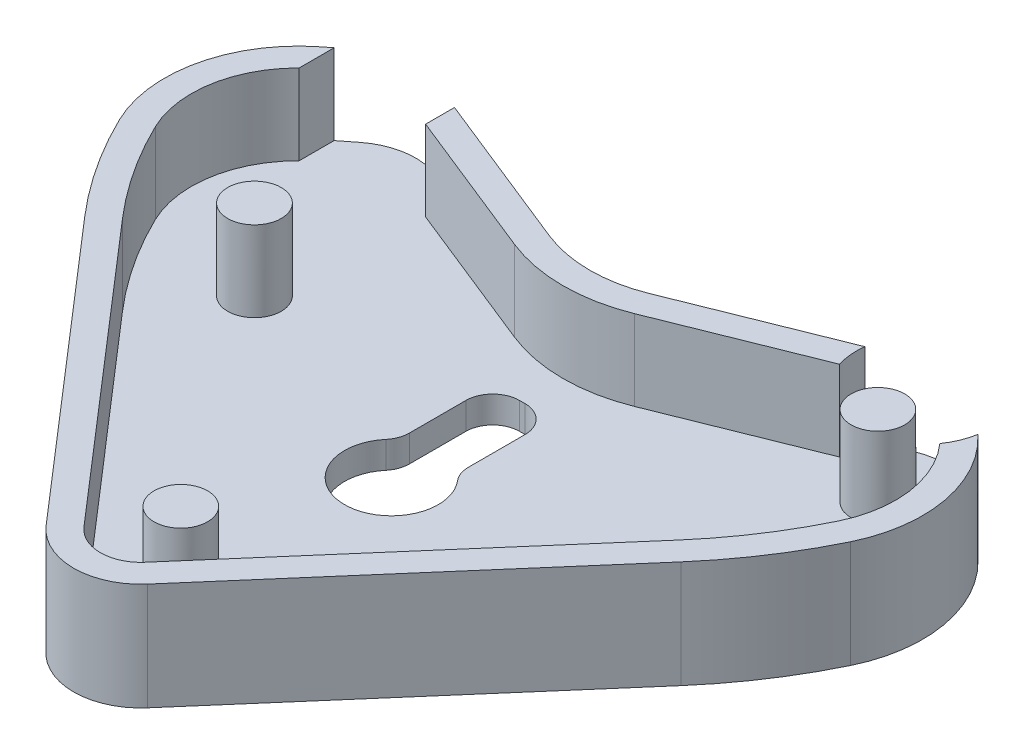
SolidWorks part; units mm, degrees
ref_plane "Alzado" through (0, 0, 0) normal (0, 0, 1) x (1, 0, 0)
ref_plane "Planta" through (0, 0, 0) normal (0, 1, 0) x (1, 0, 0)
ref_plane "Vista lateral" through (0, 0, 0) normal (1, 0, 0) x (0, 0, -1)
sketch "Croquis1" plane through (0, 0, 0) normal (0, 1, 0) x (1, 0, 0)
  line L0 (0, 0) -> (0, -34.6622) construction
  line L1 (0, 0) -> (-30, 0) construction
  line L2 (0, 0) -> (30, 0) construction
  line L3 (0, 0) -> (0, 11.4382) construction
  line L4 (-30, 0) -> (-30, 6.56)
  line L5 (-30, 6.56) -> (-20.5613, 13.9702)
  line L6 (-20.5613, 13.9702) -> (0, 5.7191)
  line L7 (0, 5.7191) -> (20.5613, 13.9702)
  line L8 (20.5613, 13.9702) -> (30, 6.56)
  line L9 (30, 6.56) -> (30, 0)
  line L10 (-30, 0) -> (0, -34.6622)
  line L11 (0, -34.6622) -> (30, 0)
  dimension "D1" = 30
  dimension "D2" = 30
  dimension "D3" = 12
  dimension "D4" = 12
  dimension "D5" = 120
  dimension "D6" = 120
extrude "Saliente-Extruir1" add sketch "Croquis1" along normal blind 8
fillet "Redondeo3" radius 5 1 edges at (0, 4, 34.6622)
fillet "Redondeo4" radius 5 2 edges at (20.5613, 4, -13.9702) (-20.5613, 4, -13.9702)
fillet "Redondeo5" radius 35 2 edges at (-30, 4, 0) (30, 4, 0)
fillet "Redondeo6" radius 10 2 edges at (-30, 4, -6.56) (30, 4, -6.56)
fillet "Redondeo7" radius 10 1 edges at (0, 4, -5.7191)
shell "Vaciado1" thickness 2 removed face at (0, 8, -0.3452)
sketch "Croquis2" plane through (0, 2, 0) normal (0, 1, 0) x (1, 0, 0)
  line L0 (0, 4.4942) -> (0, -30.0219) construction
  arc A0 (-4.4691, 5.3575) -> (4.4691, 5.3575) centre (0, 16.4942) ccw construction
  arc A1 (-2.2684, -28.9851) -> (2.2684, -28.9851) centre (0, -27.0219) ccw construction
  circle A2 centre (0, -24.0219) radius 2
  dimension "D2" = 4
  dimension "D1" = 6
extrude "Saliente-Extruir2" add sketch "Croquis2" along normal through all
sketch "Croquis3" plane through (0, 2, 0) normal (0, 1, 0) x (1, 0, 0)
  circle A0 centre (20.1688, 11.2246) radius 5
  arc A1 (21.5969, 10.6144) -> (18.627, 11.0389) centre (19.7443, 8.2548) ccw construction
  dimension "D1" = 10
extrude "Cortar-Extruir1" cut sketch "Croquis3" along normal blind 10
sketch "Croquis4" plane through (0, 2, 0) normal (0, 1, 0) x (1, 0, 0)
  line L0 (20.4518, 13.2044) -> (19.7443, 8.2548) construction
  line L1 (19.7443, 8.2548) -> (-19.2557, 8.2548) construction
  arc A0 (22.8319, 12.1876) -> (17.8822, 12.8951) centre (19.7443, 8.2548) ccw construction
  circle A1 centre (19.7443, 8.2548) radius 2
  dimension "D1" = 4
  dimension "D2" = 39
extrude "Saliente-Extruir4" add sketch "Croquis4" along normal through all
sketch "Croquis5" plane through (0, 2, 0) normal (0, 1, 0) x (1, 0, 0)
  line L0 (0, -24.0219) -> (0, 9.8307) construction
  line L1 (19.7443, 8.2548) -> (0, 8.2548) construction
  line L2 (0, 8.2548) -> (-19.74, 8.2548) construction
  line L3 (-23.9156, 8.2548) -> (-15.5644, 8.2548)
  line L4 (-15.5644, 8.2548) -> (-15.5644, 14.1742)
  line L5 (-15.5644, 14.1742) -> (-23.9156, 14.1742)
  line L6 (-23.9156, 14.1742) -> (-23.9156, 7.8399)
  point P11 (-19.74, 8.2548)
  line M7 (-4.4691, 5.3575) -> (-18.627, 11.0389)
  arc M8 (-18.627, 11.0389) -> (-21.5969, 10.6144) centre (-19.7443, 8.2548) ccw
  line M9 (-21.5969, 10.6144) -> (-23.2237, 9.3372)
  arc M10 (-23.2237, 9.3372) -> (-25.4814, -0.4469) centre (-18.2836, 3.0448) ccw
  dimension "D1" = 19.74
extrude "Cortar-Extruir2" cut sketch "Croquis5" along normal blind 10 contours L5 L6 L4 M10 M9 M8 M7 region at (-19.8852, 2, -12.259)
sketch "Croquis6" plane through (0, 2, 0) normal (0, 1, 0) x (1, 0, 0)
  line L0 (-16.8551, -1.6721) -> (-24.8551, -1.6721) construction
  line L1 (-16.8551, -1.6721) -> (-16.8551, 10.3279) construction
  line L2 (-4.4691, 5.3575) -> (-15.5644, 9.8099) construction
  circle A0 centre (-16.8551, -1.6721) radius 2
  arc A2 (-25.4814, -0.4469) -> (-20.7426, -7.64) centre (4.2096, 13.9561) ccw construction
  dimension "D1" = 4
  dimension "D2" = 8
  dimension "D3" = 12
extrude "Saliente-Extruir5" add sketch "Croquis6" along normal through all
sketch "Croquis7" plane through (0, 2, 0) normal (0, 1, 0) x (1, 0, 0)
  line L2 (0, 4.4942) -> (0, -30.0219) construction
  arc A0 (-4.4691, 5.3575) -> (4.4691, 5.3575) centre (0, 16.4942) ccw construction
  circle A1 centre (0, -8.3059) radius 2.5
  arc A2 (-2.2684, -28.9851) -> (2.2684, -28.9851) centre (0, -27.0219) ccw construction
  dimension "D1" = 5
  dimension "D2" = 0
extrude "Cortar-Extruir3" cut sketch "Croquis7" against normal blind 10
sketch "Croquis8" plane through (0, 2, 0) normal (0, 1, 0) x (1, 0, 0)
  line L0 (0, -5.8059) -> (0, -10.8059) construction
  line L1 (0, -8.3059) -> (0, 1.4593) construction
  line L8 (-2.2064, 1.4593) -> (2.2064, 1.4593)
  line L9 (-2.2064, 1.4593) -> (-2.2064, -8.3059)
  line L10 (-2.2064, -8.3059) -> (2.2064, -8.3059)
  line L11 (2.2064, 1.4593) -> (2.2064, -8.3059)
  line L12 (-2.2064, 1.4593) -> (2.2064, -8.3059) construction
  line L13 (-2.2064, -8.3059) -> (2.2064, 1.4593) construction
  circle A0 centre (0, -8.3059) radius 2.5 construction
  circle A1 centre (0, -8.3059) radius 3.5
  point P8 (0.0204, -2.306)
  point P9 (0, -3.4233)
  point P15 (-15.0905, 4.4882)
  circle M2 centre (0, -8.3059) radius 2.5
  dimension "D1" = 7
extrude "Cortar-Extruir4" cut sketch "Croquis8" against normal blind 5 contours A1 L11 L8 L9 | L9 A1 L11 M2 | L11 A1 L9 M2 region at (0, 2, 1.8014) region at (0, 2, 5.6574) region at (-2.3, 2, 6.3597)
fillet "Redondeo8" radius 2 4 edges at (2.2064, 1, 5.589) (-2.2064, 1, 5.589) (2.2064, 1, -1.4593) (-2.2064, 1, -1.4593)
